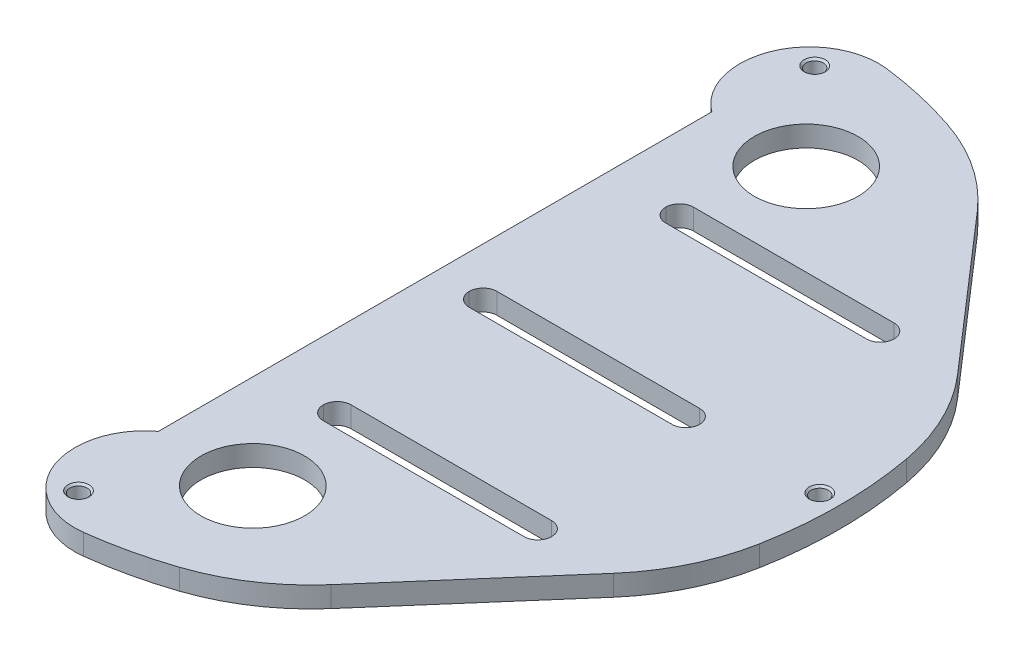
SolidWorks part; units mm, degrees
ref_plane "前视基准面" through (0, 0, 0) normal (0, 0, 1) x (1, 0, 0)
ref_plane "上视基准面" through (0, 0, 0) normal (0, 1, 0) x (1, 0, 0)
ref_plane "右视基准面" through (0, 0, 0) normal (1, 0, 0) x (0, 0, -1)
other "Configuration Table"
sketch "草图1" plane through (0, 0, 0) normal (0, 1, 0) x (1, 0, 0)
  line L0 (-4, 58.3631) -> (-4, -58.3631)
  arc A0 (-4, -58.3631) -> (-4, 58.3631) centre (0, 0) ccw
  dimension "D1" = 117
  dimension "D2" = 4
extrude "凸台-拉伸1" add sketch "草图1" along normal blind 3
fillet "圆角1" radius 10 2 edges at (-4, 1.5, 58.3631) (-4, 1.5, -58.3631)
sketch "草图2" plane through (0, 0, 0) normal (0, -1, 0) x (1, 0, 0)
  line L1 (8.6035, 22.75) -> (41.6035, 22.75)
  line L2 (8.6035, 22.75) -> (8.6035, 26.75)
  line L3 (8.6035, 26.75) -> (41.6035, 26.75)
  line L4 (41.6035, 22.75) -> (41.6035, 26.75)
  line L5 (8.6035, 22.75) -> (41.6035, 26.75) construction
  line L6 (8.6035, 26.75) -> (41.6035, 22.75) construction
  line L7 (0, 0) -> (78.1975, 0) construction
  line L8 (8.6035, -26.75) -> (41.6035, -22.75) construction
  line L9 (8.6035, -22.75) -> (41.6035, -26.75) construction
  line L10 (41.6035, -22.75) -> (41.6035, -26.75)
  line L11 (8.6035, -26.75) -> (41.6035, -26.75)
  line L12 (8.6035, -22.75) -> (8.6035, -26.75)
  line L13 (8.6035, -22.75) -> (41.6035, -22.75)
  line L15 (4.9398, 2) -> (38.2488, 2)
  line L16 (4.9398, 2) -> (4.9398, -2)
  line L17 (4.9398, -2) -> (38.2488, -2)
  line L18 (38.2488, 2) -> (38.2488, -2)
  line L19 (4.9398, 2) -> (38.2488, -2) construction
  line L20 (4.9398, -2) -> (38.2488, 2) construction
  point P0 (25.1035, 24.75)
  point P14 (25.1035, -24.75)
  dimension "D2" = 4
  dimension "D3" = 33
  dimension "D4" = 4
extrude "切除-拉伸1" cut sketch "草图2" against normal through all
sketch "草图3" plane through (0, 0, 0) normal (0, -1, 0) x (1, 0, 0)
  line L0 (-4, -48.1274) -> (-4, 48.1274) construction
  line L1 (-8, -40) -> (0, -40)
  line L2 (-8, -40) -> (-8, 40)
  line L3 (-8, 40) -> (0, 40)
  line L4 (0, -40) -> (0, 40)
  line L5 (-8, -40) -> (0, 40) construction
  line L6 (-8, 40) -> (0, -40) construction
  point P0 (-4, 0)
  dimension "D1" = 8
  dimension "D2" = 80
extrude "切除-拉伸2" cut sketch "草图3" against normal through all
fillet "圆角2" radius 10 2 edges at (-4, 1.5, 40) (-4, 1.5, -40)
fillet "圆角3" radius 2 12 edges at (8.6035, 1.5, -26.75) (8.6035, 1.5, -22.75) (41.6035, 1.5, -26.75) (41.6035, 1.5, -22.75) (4.9398, 1.5, 2) (38.2488, 1.5, 2) (38.2488, 1.5, -2) (4.9398, 1.5, -2) (41.6035, 1.5, 22.75) (41.6035, 1.5, 26.75) (8.6035, 1.5, 22.75) (8.6035, 1.5, 26.75)
sketch "草图4" plane through (0, 3, 0) normal (0, 1, 0) x (1, 0, 0)
  line L0 (55.0267, -19.8574) -> (27.2997, -51.7395)
  line L1 (0, 0) -> (58.5, 0) construction
  line L2 (55.0267, 19.8574) -> (27.2997, 51.7395)
  arc A0 (7.2371, -58.0506) -> (7.2371, 58.0506) centre (0, 0) ccw construction
  arc A1 (27.2997, -51.7395) -> (55.0267, -19.8574) centre (0, 0) ccw
  arc A2 (27.2997, 51.7395) -> (55.0267, 19.8574) centre (0, 0) cw
extrude "切除-拉伸3" cut sketch "草图4" against normal through all
fillet "圆角4" radius 30 4 edges at (27.2997, 1.5, 51.7395) (55.0267, 1.5, 19.8574) (55.0267, 1.5, -19.8574) (27.2997, 1.5, -51.7395)
sketch "草图5" plane through (0, 3, 0) normal (0, 1, 0) x (1, 0, 0)
  circle A0 centre (13.6503, 40) radius 7.5
  circle A1 centre (13.6503, -40) radius 7.5
  dimension "D1" = 15
  dimension "D2" = 15
extrude "切除-拉伸4" cut sketch "草图5" against normal through all
sketch "草图6" plane through (0, 3, 0) normal (0, 1, 0) x (1, 0, 0)
  line L0 (0, 0) -> (58.5, 0) construction
  point P0 (1.6686, 53.2134)
  point P1 (1.6686, -53.2134)
  point P5 (0.7923, -68.4636)
  point P14 (55.5261, 0.0866)
hole_wizard "M3 螺纹孔1" positions "草图6" profile "草图7" tap size "M3" standard "GB"
sketch "草图7" plane through (1.6686, 3, -53.2134) normal (1, 0, 0) x (0, 0, 1)
  line L0 (0, 0) -> (0, 3.7511)
  line L1 (0, 3.7511) -> (1.25, 3)
  line L2 (1.25, 3) -> (1.25, 0.275)
  line L3 (1.25, 0.275) -> (1.525, 0)
  line L5 (1.525, 0) -> (0, 0)
  line L6 (-1.25, 0.275) -> (-1.525, 0) construction
  line L10 (0, 3.7511) -> (-1.25, 3) construction
  line L11 (0, -6.35) -> (0, 107.95) construction
  dimension "螺纹孔钻头直径" = 2.5
  dimension "螺纹孔钻头深度" = 3
  dimension "近端锥形沉头孔直径" = 3.05
  dimension "近端锥形沉头孔角度" = 90
  dimension "导头角度" = 118
cosmetic thread "孔螺蚊线1" parameters "D1"=2.4, "D2"=3
cosmetic thread "孔螺蚊线2" parameters "D1"=2.4, "D2"=3
cosmetic thread "孔螺蚊线3" parameters "D1"=2.4, "D2"=3
